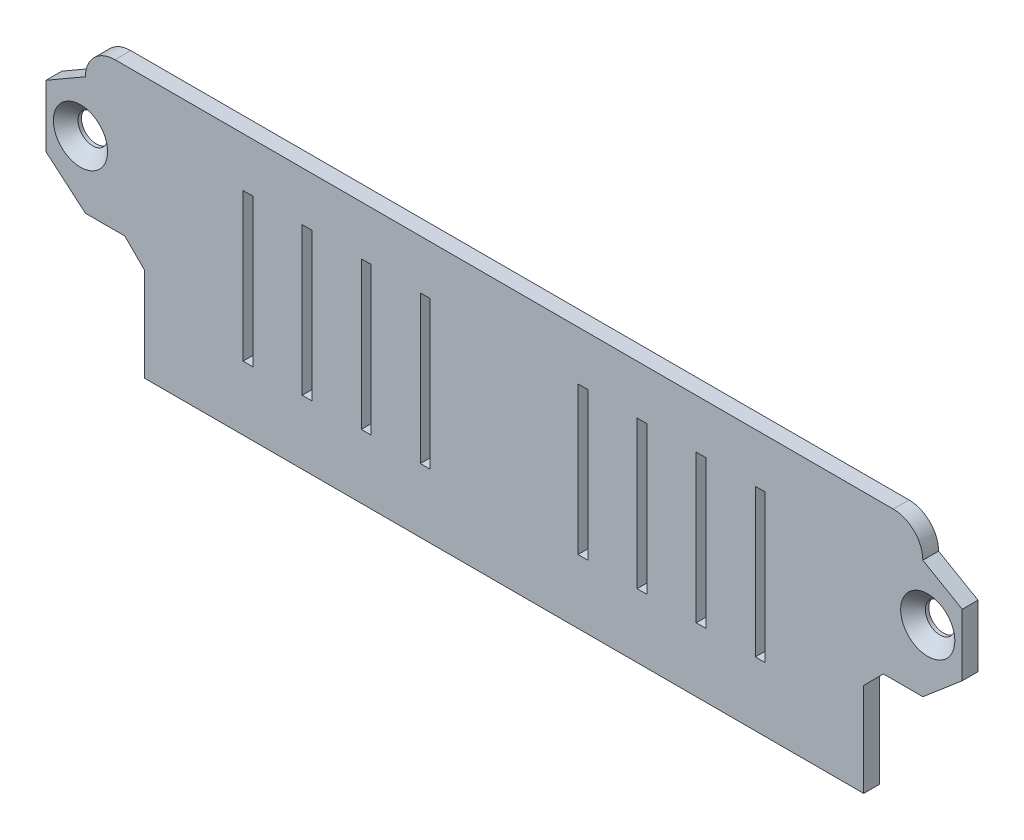
SolidWorks part; units mm, degrees
ref_plane "Ebene vorne" through (0, 0, 0) normal (0, 0, 1) x (1, 0, 0)
ref_plane "Ebene oben" through (0, 0, 0) normal (0, 1, 0) x (1, 0, 0)
ref_plane "Ebene rechts" through (0, 0, 0) normal (1, 0, 0) x (0, 0, -1)
sketch "Sketch1" plane through (0, 0, 0) normal (0, 0, 1) x (1, 0, 0)
  line L1 (-42.5, 43.7773) -> (42.5, 43.7773)
  line L2 (-46.5, 38.4675) -> (-46.5, 32.1773)
  line L3 (-36.5, 17.2773) -> (36.5, 17.2773)
  line L4 (46.5, 38.4675) -> (46.5, 32.1773)
  line L5 (0, 17.2773) -> (0, 30.5179) construction
  line L6 (-46.5, 35.3224) -> (-43.3628, 35.3224) construction
  line L8 (-46.5, 38.4675) -> (-42.5, 40.7773)
  line L9 (-42.5, 40.7773) -> (-42.5, 43.7773)
  line L10 (-46.5, 32.1773) -> (-42.5, 28.7773)
  line L11 (-42.5, 28.7773) -> (-38.5, 28.7773)
  line L12 (-38.5, 28.7773) -> (-36.5, 26.7773)
  line L13 (-36.5, 26.7773) -> (-36.5, 17.2773)
  line L15 (46.5, 32.1773) -> (42.5, 28.7773)
  line L17 (42.5, 28.7773) -> (38.5, 28.7773)
  line L18 (38.5, 28.7773) -> (36.5, 26.7773)
  line L19 (36.5, 26.7773) -> (36.5, 17.2773)
  line L21 (46.5, 38.4675) -> (42.5, 40.7773)
  line L22 (42.5, 40.7773) -> (42.5, 43.7773)
  circle A0 centre (-43, 35.3224) radius 1.5
  circle A1 centre (43, 35.3224) radius 1.5
  dimension "D6" = 3
  dimension "D1" = 85
  dimension "D2" = 73
  dimension "D3" = 225
  dimension "D4" = 12
  dimension "D5" = 6.2902
  dimension "D7" = 3.5
  dimension "D8" = 12
  dimension "D9" = 6.2902
  dimension "D10" = 225
  dimension "D11" = 3
  dimension "D12" = 3
  dimension "D13" = 9.5
extrude "Boss-Extrude1" add sketch "Sketch1" along normal blind 1.6
fillet "Fillet1" radius 3 1 edges at (42.5, 43.7773, 0.8) type face fillet first side face at (0, 43.7773, 0.8) second side face at (42.5, 42.2773, 0.8)
fillet "Fillet2" radius 3 1 edges at (-42.5, 43.7773, 0.8) type face fillet first side face at (-42.5, 42.2773, 0.8) second side face at (-1.5, 43.7773, 0.8)
sketch "Sketch2" plane through (0, 0, 1.6) normal (0, 0, 1) x (1, 0, 0)
  circle A0 centre (-43, 35.3224) radius 2.75
  circle A1 centre (43, 35.3224) radius 2.75
  dimension "D1" = 5.5
extrude "Screw Heads" cut sketch "Sketch2" against normal blind 2 draft 45
sketch "Sketch3" plane through (0, 0, 1.6) normal (0, 0, 1) x (1, 0, 0)
  line L0 (39.5, 43.7773) -> (-39.5, 43.7773) construction
  line L1 (-26.5, 38.7773) -> (-25.5, 38.7773)
  line L2 (-26.5, 38.7773) -> (-26.5, 23.7773)
  line L3 (-26.5, 23.7773) -> (-25.5, 23.7773)
  line L4 (-25.5, 38.7773) -> (-25.5, 23.7773)
  line L5 (-20.5, 38.7773) -> (-19.5, 38.7773)
  line L6 (-20.5, 38.7773) -> (-20.5, 23.7773)
  line L7 (-20.5, 23.7773) -> (-19.5, 23.7773)
  line L8 (-19.5, 38.7773) -> (-19.5, 23.7773)
  line L9 (-14.5, 38.7773) -> (-13.5, 38.7773)
  line L10 (-14.5, 38.7773) -> (-14.5, 23.7773)
  line L11 (-14.5, 23.7773) -> (-13.5, 23.7773)
  line L12 (-13.5, 38.7773) -> (-13.5, 23.7773)
  line L13 (0, 17.2773) -> (0, 33.3328) construction
  line L14 (-8.5, 38.7773) -> (-7.5, 38.7773)
  line L15 (-8.5, 38.7773) -> (-8.5, 23.7773)
  line L16 (-8.5, 23.7773) -> (-7.5, 23.7773)
  line L17 (-7.5, 38.7773) -> (-7.5, 23.7773)
  line L18 (-36.5, 17.2773) -> (36.5, 17.2773) construction
  line L19 (7.5, 38.7773) -> (7.5, 23.7773)
  line L20 (8.5, 23.7773) -> (7.5, 23.7773)
  line L21 (8.5, 38.7773) -> (8.5, 23.7773)
  line L22 (8.5, 38.7773) -> (7.5, 38.7773)
  line L23 (13.5, 38.7773) -> (13.5, 23.7773)
  line L24 (14.5, 23.7773) -> (13.5, 23.7773)
  line L25 (14.5, 38.7773) -> (14.5, 23.7773)
  line L26 (14.5, 38.7773) -> (13.5, 38.7773)
  line L27 (19.5, 38.7773) -> (19.5, 23.7773)
  line L28 (20.5, 23.7773) -> (19.5, 23.7773)
  line L29 (20.5, 38.7773) -> (20.5, 23.7773)
  line L30 (20.5, 38.7773) -> (19.5, 38.7773)
  line L31 (25.5, 38.7773) -> (25.5, 23.7773)
  line L32 (26.5, 23.7773) -> (25.5, 23.7773)
  line L33 (26.5, 38.7773) -> (26.5, 23.7773)
  line L34 (26.5, 38.7773) -> (25.5, 38.7773)
  dimension "D1" = 1
  dimension "D2" = 5
  dimension "D3" = 5
  dimension "D4" = 5
  dimension "D5" = 5
  dimension "D6" = 15
  dimension "D7" = 10
extrude "Air Vents" cut sketch "Sketch3" against normal blind 2
